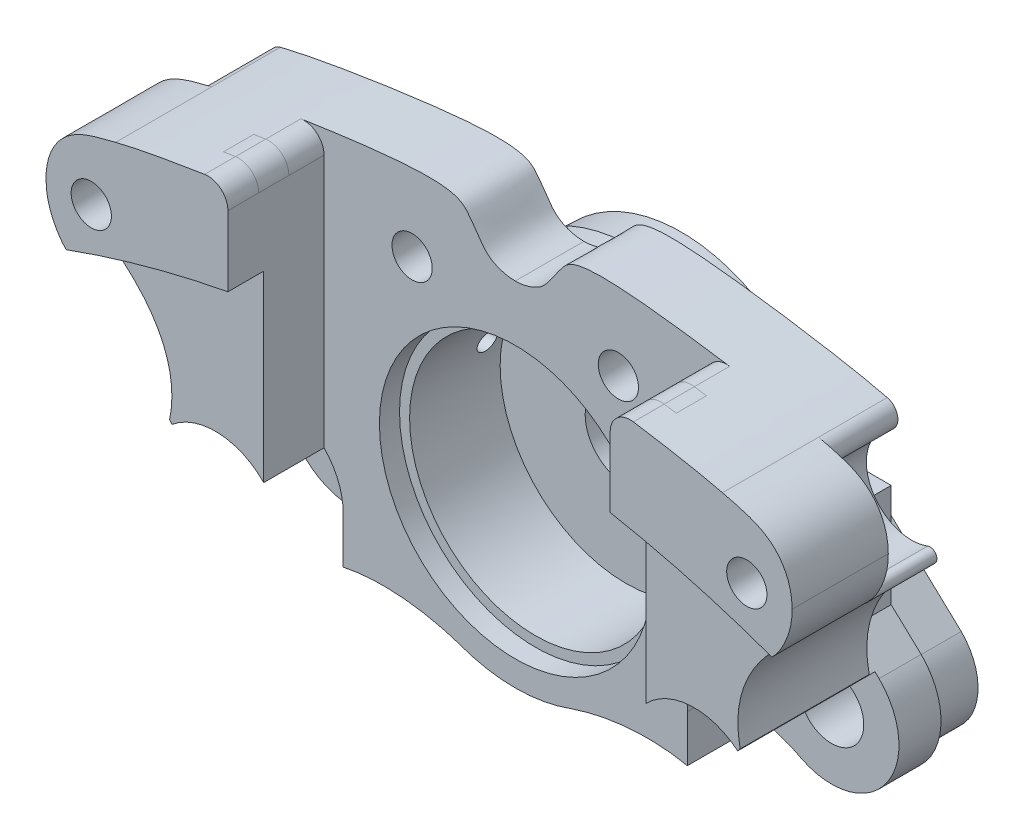
SolidWorks part; units mm, degrees
material "6061 Alloy"
ref_plane "Front Plane" through (0, 0, 0) normal (0, 0, 1) x (1, 0, 0)
ref_plane "Top Plane" through (0, 0, 0) normal (0, 1, 0) x (1, 0, 0)
ref_plane "Right Plane" through (0, 0, 0) normal (1, 0, 0) x (0, 0, -1)
sketch "Sketch1" plane through (0, 0, 0) normal (0, 0, 1) x (1, 0, 0)
  circle A0 centre (0, 0) radius 9.7028
  dimension "D1" = 19.4056
extrude "Boss-Extrude1" add sketch "Sketch1" along normal blind 4.8514
sketch "Sketch2" plane through (0, 0, 4.8514) normal (0, 0, 1) x (1, 0, 0)
  line L0 (0, 15.875) -> (0, -12.065) construction
  line L1 (-30.226, -12.065) -> (30.226, -12.065) construction
  line L2 (-13.4704, 13.4704) -> (-35.3447, -6.9463)
  line L3 (13.4704, 13.4704) -> (35.3447, -6.9463)
  line L4 (0, 0) -> (13.4704, 13.4704) construction
  line L5 (0, 0) -> (-13.4704, 13.4704) construction
  line L8 (15.9939, -16.129) -> (17.3992, -16.129) construction
  line L14 (-17.3992, -16.129) -> (-15.9939, -16.129) construction
  arc A1 (-6.8392, -17.78) -> (6.8392, -17.78) centre (0, 0) ccw
  arc A4 (26.7503, -18.415) -> (35.3447, -6.9463) centre (30.226, -12.065) ccw
  arc A5 (-35.3447, -6.9463) -> (-26.7503, -18.415) centre (-30.226, -12.065) ccw
  arc A7 (13.4704, 13.4704) -> (-13.4704, 13.4704) centre (0, 0) ccw
  spline S0 degree 3 poles (-26.7503, -18.415) (-20.9125, -15.2196) (-12.826, -15.7036) (-6.8392, -17.78) knots 0 0 0 0 1 1 1 1
  spline S1 degree 3 poles (26.7503, -18.415) (20.9125, -15.2196) (12.826, -15.7036) (6.8392, -17.78) knots 0 0 0 0 1 1 1 1
  dimension "D2" = 38.1
  dimension "D6" = 6.35
  dimension "D3" = 27.94
  dimension "D4" = 60.452
  dimension "D5" = 30.226
  dimension "D9" = 17.78
extrude "Boss-Extrude2" add sketch "Sketch2" along normal blind 1.778 and the other way blind 4.1656
sketch "Sketch3" plane through (0, 0, 6.6294) normal (0, 0, 1) x (1, 0, 0)
  line L0 (-14.3527, 14.3841) -> (-18.4698, 10.5414)
  line L1 (36.2267, -6.0322) -> (32.4398, -2.4977)
  line L2 (18.4698, 10.5414) -> (14.3527, 14.3841)
  line L6 (0, 19.05) -> (0, -19.05) construction
  line L7 (18.4698, 10.5414) -> (32.4398, 10.5414)
  line L8 (32.4398, 10.5414) -> (32.4398, -2.4977)
  line L9 (-32.4398, 10.5414) -> (-32.4398, -2.4977)
  line L10 (-18.4698, 10.5414) -> (-32.4398, 10.5414)
  line L11 (-32.4398, -2.4977) -> (-36.2267, -6.0322)
  arc A0 (-36.2267, -6.0322) -> (-26.4195, -19.6751) centre (-30.226, -12.065) ccw
  arc A1 (-7.0511, -19.0574) -> (7.0511, -19.0574) centre (0, 0) ccw
  arc A2 (26.4195, -19.6751) -> (36.2267, -6.0322) centre (30.226, -12.065) ccw
  arc A3 (14.3527, 14.3841) -> (-14.3527, 14.3841) centre (0, 0) ccw
  circle A12 centre (0, 0) radius 15.875 construction
  spline S6 degree 3 poles (-26.4195, -19.6751) (-25.7261, -19.2934) (-24.2904, -18.6475) (-21.15, -17.7332) (-17.755, -17.383) (-14.3154, -17.5158) (-11.771, -17.8352) (-9.7297, -18.2634) (-8.1656, -18.6925) (-7.4233, -18.9297) (-7.0511, -19.0574) knots 0 0 0 0 0.124858 0.249716 0.499432 0.62429 0.749148 0.874006 0.936435 0.998864 0.998864 0.998864 0.998864
  spline S7 degree 3 poles (7.0511, -19.0574) (7.4233, -18.9297) (8.1656, -18.6925) (9.7297, -18.2634) (11.771, -17.8352) (14.3154, -17.5158) (17.755, -17.383) (21.15, -17.7332) (24.2904, -18.6475) (25.7261, -19.2934) (26.4195, -19.6751) knots 0.001136 0.001136 0.001136 0.001136 0.063565 0.125994 0.250852 0.37571 0.500568 0.750284 0.875142 1 1 1 1
  dimension "D3" = 31.75
  dimension "D4" = 13.97
extrude "Boss-Extrude3" add sketch "Sketch3" along normal blind 6.35
sketch "Sketch5" plane through (0, 0, 12.9794) normal (0, 0, 1) x (1, 0, 0)
  line L0 (-41.3748, 17.9058) -> (0, 17.9058) construction
  line L1 (0, 0) -> (0, 17.9058) construction
  line L2 (0, 17.9058) -> (0, 24.1687) construction
  line L3 (1.2486, 24.1687) -> (-1.2486, 24.1687) construction
  line L4 (-35.6955, -5.5467) -> (-36.0146, -5.1665)
  line L5 (35.6955, -5.5467) -> (36.0146, -5.1665)
  line L7 (-30.226, -12.065) -> (30.226, -12.065) construction
  line L8 (-21.717, -12.065) -> (-21.717, -17.9655)
  line L9 (21.717, -12.065) -> (21.717, -17.9655)
  arc A0 (-43.3944, 12.5595) -> (-38.6973, 22.9547) centre (-41.3748, 17.9058) ccw
  arc A1 (-43.3944, 12.5595) -> (-44.0085, 10.9339) centre (-43.7015, 11.7467) ccw
  arc A2 (43.3944, 12.5595) -> (44.0085, 10.9339) centre (43.7015, 11.7467) cw
  arc A3 (-7.0511, -19.0574) -> (7.0511, -19.0574) centre (0, 0) ccw construction
  arc A4 (38.2982, 26.2485) -> (38.6973, 22.9547) centre (37.8646, 24.5249) cw
  arc A5 (-38.2982, 26.2485) -> (-38.6973, 22.9547) centre (-37.8646, 24.5249) ccw
  arc A6 (43.3944, 12.5595) -> (38.6973, 22.9547) centre (41.3748, 17.9058) cw
  arc A7 (-7.0511, -19.0574) -> (7.0511, -19.0574) centre (0, 0) ccw
  arc A8 (35.6955, -5.5467) -> (21.717, -12.065) centre (30.226, -12.065) ccw
  arc A9 (-21.717, -12.065) -> (-35.6955, -5.5467) centre (-30.226, -12.065) ccw
  arc A10 (-36.2267, -6.0322) -> (-26.4195, -19.6751) centre (-30.226, -12.065) ccw construction
  arc A11 (26.4195, -19.6751) -> (36.2267, -6.0322) centre (30.226, -12.065) ccw construction
  spline S0 degree 3 poles (-38.2982, 26.2485) (-33.1754, 27.5373) (-13.115, 30.6549) (-7.0965, 29.9705) (-4.5847, 26.9765) (-3.9197, 25.0203) (-1.0614, 24.1687) (0, 24.1687) knots 0.095992 0.095992 0.095992 0.095992 0.290427 0.440824 0.493566 0.817843 1 1 1 1
  spline S1 degree 3 poles (-44.0085, 10.9339) (-41.4119, 8.9019) (-37.0603, 4.9292) (-35.1847, -1.262) (-36.0146, -5.1665) knots 0.120959 0.120959 0.120959 0.120959 0.469292 0.87789 0.87789 0.87789 0.87789
  spline S2 degree 3 poles (44.0085, 10.9339) (41.4119, 8.9019) (37.0603, 4.9292) (35.1847, -1.262) (36.0146, -5.1665) knots 0.120959 0.120959 0.120959 0.120959 0.469292 0.87789 0.87789 0.87789 0.87789
  spline S3 degree 3 poles (38.2982, 26.2485) (33.1754, 27.5373) (13.115, 30.6549) (7.0965, 29.9705) (4.5847, 26.9765) (3.9197, 25.0203) (1.0614, 24.1687) (0, 24.1687) knots 0.095992 0.095992 0.095992 0.095992 0.290427 0.440824 0.493566 0.817843 1 1 1 1
  spline S5 degree 3 poles (-978.7255, -1777.5091) (-16.9448, -159.6111) (-62.0704, -29.6471) (-21.15, -17.7332) (-17.755, -17.383) (-14.3154, -17.5158) (-11.771, -17.8352) (-9.7297, -18.2634) (13.3146, -24.5869) (3.4509, -48.9429) (1868.6439, -712.6762) knots -6.008282 -6.008282 -6.008282 -6.008282 0.124858 0.249716 0.499432 0.62429 0.749148 0.874006 0.936435 4.428366 4.428366 4.428366 4.428366 only from (-26.4195, -19.6751) to (-7.0511, -19.0574) construction
  spline S6 degree 3 poles (7.0511, -19.0574) (7.4233, -18.9297) (8.1656, -18.6925) (9.7297, -18.2634) (11.771, -17.8352) (14.3154, -17.5158) (17.6851, -17.3857) (20.1633, -17.6317) (21.717, -17.9655) knots 0.001136 0.001136 0.001136 0.001136 0.063565 0.125994 0.250852 0.37571 0.500568 0.740144 0.740144 0.740144 0.740144
  spline S7 degree 3 poles (-21.717, -17.9655) (-20.1633, -17.6317) (-17.6851, -17.3857) (-14.3154, -17.5158) (-11.771, -17.8352) (-9.7297, -18.2634) (-8.1656, -18.6925) (-7.4233, -18.9297) (-7.0511, -19.0574) knots 0.259856 0.259856 0.259856 0.259856 0.499432 0.62429 0.749148 0.874006 0.936435 0.998864 0.998864 0.998864 0.998864
  dimension "D1" = 130
  dimension "D2" = 130
extrude "Boss-Extrude6" add sketch "Sketch5" along normal blind 8.6614
sketch "Sketch6" plane through (0, 0, 21.6408) normal (0, 0, 1) x (1, 0, 0)
  line L0 (0, 0) -> (0, 15.7134) construction
  line L2 (-36.0146, -5.1665) -> (-35.6955, -5.5467) construction
  line L3 (-36.0146, -5.1665) -> (-35.6955, -5.5467)
  line L4 (-36.0146, -5.1665) -> (-35.6955, -5.5467)
  line L5 (35.6955, -5.5467) -> (36.0146, -5.1665) construction
  line L6 (35.6955, -5.5467) -> (36.0146, -5.1665)
  line L11 (-21.717, -12.065) -> (-21.717, -17.9655)
  line L12 (-21.717, -12.065) -> (-21.717, -17.9655)
  line L13 (21.717, -17.9655) -> (21.717, -12.065)
  line L14 (21.717, -17.9655) -> (21.717, -12.065)
  line L15 (35.6955, -5.5467) -> (36.0146, -5.1665)
  arc A0 (-7.0511, -19.0574) -> (7.0511, -19.0574) centre (0, 0) ccw construction
  arc A2 (-7.0511, -19.0574) -> (7.0511, -19.0574) centre (0, 0) ccw
  arc A9 (-38.2982, 26.2485) -> (-38.6973, 22.9547) centre (-37.8646, 24.5249) ccw
  arc A10 (-43.3944, 12.5595) -> (-38.6973, 22.9547) centre (-41.3748, 17.9058) ccw
  arc A11 (-43.3944, 12.5595) -> (-44.0085, 10.9339) centre (-43.7015, 11.7467) ccw
  arc A12 (-21.717, -12.065) -> (-35.6955, -5.5467) centre (-30.226, -12.065) ccw
  arc A14 (-21.717, -12.065) -> (-35.6955, -5.5467) centre (-30.226, -12.065) ccw
  arc A15 (44.0085, 10.9339) -> (43.3944, 12.5595) centre (43.7015, 11.7467) ccw
  arc A16 (38.6973, 22.9547) -> (43.3944, 12.5595) centre (41.3748, 17.9058) ccw
  arc A17 (38.6973, 22.9547) -> (38.2982, 26.2485) centre (37.8646, 24.5249) ccw
  arc A19 (-7.0511, -19.0574) -> (7.0511, -19.0574) centre (0, 0) ccw
  arc A25 (35.6955, -5.5467) -> (21.717, -12.065) centre (30.226, -12.065) ccw
  arc A26 (35.6955, -5.5467) -> (21.717, -12.065) centre (30.226, -12.065) ccw
  spline S0 degree 3 poles (-38.2982, 26.2485) (-40.3087, 25.7427) (-44.7917, 24.769) (-47.0898, 20.7135) (-47.0898, 17.9058) knots 0 0 0 0 0.465439 1 1 1 1
  spline S1 degree 3 poles (-47.0898, 17.9058) (-47.0898, 16.2266) (-46.4199, 13.9412) (-45.0511, 11.7499) (-44.0085, 10.9339) knots 0 0 0 0 0.544279 1 1 1 1
  spline S2 degree 3 poles (47.0898, 17.9058) (47.0898, 16.2266) (46.4199, 13.9412) (45.0511, 11.7499) (44.0085, 10.9339) knots 0 0 0 0 0.544279 1 1 1 1
  spline S3 degree 3 poles (38.2982, 26.2485) (40.3087, 25.7427) (44.7917, 24.769) (47.0898, 20.7135) (47.0898, 17.9058) knots 0 0 0 0 0.465439 1 1 1 1
  spline S4 degree 3 poles (-657.2117, 1910.6164) (-193.2792, -28.4777) (64.9588, 100.6233) (-94.862, -144.8705) (-2021.4839, -219.0001) knots -4.624316 -4.624316 -4.624316 -4.624316 0.469292 5.21147 5.21147 5.21147 5.21147 only from (-44.0085, 10.9339) to (-36.0146, -5.1665) construction
  spline S6 degree 3 poles (-2183.245, 2077.1816) (166.4827, 62.4672) (0.5629, 11.8331) (-4.5847, 26.9765) (-7.0965, 29.9705) (-30.8647, 32.6733) (-341.1745, -36.5716) (2935.9323, 415.7326) knots -3.67352 -3.67352 -3.67352 -3.67352 0.278149 0.602426 0.655168 0.805566 2.172513 2.172513 2.172513 2.172513 only from (0, 24.1687) to (-38.2982, 26.2485)
  spline S7 degree 3 poles (-408.6307, 942.0868) (-142.5011, -5.0132) (25.7847, 65.0404) (-66.3745, -98.2734) (-1022.8759, -166.7155) knots -3.564937 -3.564937 -3.564937 -3.564937 0.469292 4.198398 4.198398 4.198398 4.198398 only from (-44.0085, 10.9339) to (-36.0146, -5.1665)
  spline S8 degree 3 poles (773.9984, -623.6344) (-88.6459, -105.5622) (-56.1182, -15.9019) (-14.3154, -17.5158) (-11.771, -17.8352) (-9.7297, -18.2634) (8.744, -23.3327) (6.1469, -39.711) (927.5284, -374.7025) knots -5.320743 -5.320743 -5.320743 -5.320743 0.499432 0.62429 0.749148 0.874006 0.936435 3.698622 3.698622 3.698622 3.698622 only from (-21.717, -17.9655) to (-7.0511, -19.0574)
  spline S10 degree 3 poles (1022.878, -166.7156) (66.3745, -98.2735) (-25.7847, 65.0403) (142.501, -5.0132) (408.6302, 942.085) knots -3.199551 -3.199551 -3.199551 -3.199551 0.529557 4.563784 4.563784 4.563784 4.563784 only from (36.0146, -5.1665) to (44.0085, 10.9339)
  spline S11 degree 3 poles (-2936.0853, 415.7537) (341.1832, -36.5735) (30.865, 32.6733) (7.0965, 29.9705) (4.5847, 26.9765) (-0.5628, 11.8332) (-166.4811, 62.4666) (2183.2062, 2077.1484) knots -1.076542 -1.076542 -1.076542 -1.076542 0.290427 0.440824 0.493566 0.817843 4.76949 4.76949 4.76949 4.76949 only from (38.2982, 26.2485) to (0, 24.1687)
  spline S12 degree 3 poles (0, 24.1687) (-1.0614, 24.1687) (-3.9197, 25.0203) (-4.5847, 26.9765) (-7.0965, 29.9705) (-13.115, 30.6549) (-33.1754, 27.5373) (-38.2982, 26.2485) knots 0.095992 0.095992 0.095992 0.095992 0.278149 0.602426 0.655168 0.805566 1 1 1 1
  spline S13 degree 3 poles (2021.4462, -218.9987) (94.861, -144.8689) (-64.9585, 100.6237) (193.281, -28.4786) (657.2209, 1910.6551) knots -4.212589 -4.212589 -4.212589 -4.212589 0.529557 5.6232 5.6232 5.6232 5.6232 only from (36.0146, -5.1665) to (44.0085, 10.9339) construction
  spline S14 degree 3 poles (-44.0085, 10.9339) (-41.4119, 8.9019) (-37.0603, 4.9292) (-35.1847, -1.262) (-36.0146, -5.1665) knots 0.120959 0.120959 0.120959 0.120959 0.469292 0.87789 0.87789 0.87789 0.87789
  spline S15 degree 3 poles (-1868.6977, -712.6953) (-3.4507, -48.9434) (-13.3148, -24.587) (9.7297, -18.2634) (11.771, -17.8352) (14.3154, -17.5158) (66.5225, -15.5003) (104.6343, -157.023) (-1642.0572, -1120.0359) knots -3.428399 -3.428399 -3.428399 -3.428399 0.063565 0.125994 0.250852 0.37571 0.500568 7.831491 7.831491 7.831491 7.831491 only from (7.0511, -19.0574) to (21.717, -17.9655) construction
  spline S16 degree 3 poles (1642.0265, -1120.019) (-104.6338, -157.0214) (-66.5222, -15.5003) (-14.3154, -17.5158) (-11.771, -17.8352) (-9.7297, -18.2634) (13.3145, -24.5869) (3.451, -48.9427) (1868.6163, -712.6663) knots -6.831448 -6.831448 -6.831448 -6.831448 0.499432 0.62429 0.749148 0.874006 0.936435 4.428348 4.428348 4.428348 4.428348 only from (-21.717, -17.9655) to (-7.0511, -19.0574) construction
  spline S17 degree 3 poles (38.2982, 26.2485) (33.1754, 27.5373) (13.115, 30.6549) (7.0965, 29.9705) (4.5847, 26.9765) (3.9197, 25.0203) (1.0614, 24.1687) (0, 24.1687) knots 0.095992 0.095992 0.095992 0.095992 0.290427 0.440824 0.493566 0.817843 1 1 1 1
  spline S18 degree 3 poles (36.0146, -5.1665) (35.1847, -1.262) (37.0603, 4.9292) (41.4119, 8.9019) (44.0085, 10.9339) knots 0.120959 0.120959 0.120959 0.120959 0.529557 0.87789 0.87789 0.87789 0.87789
  spline S19 degree 3 poles (7.0511, -19.0574) (7.4233, -18.9297) (8.1656, -18.6925) (9.7297, -18.2634) (11.771, -17.8352) (14.3154, -17.5158) (17.6851, -17.3857) (20.1633, -17.6317) (21.717, -17.9655) knots 0.001136 0.001136 0.001136 0.001136 0.063565 0.125994 0.250852 0.37571 0.500568 0.740144 0.740144 0.740144 0.740144
  spline S20 degree 3 poles (-21.717, -17.9655) (-20.1633, -17.6317) (-17.6851, -17.3857) (-14.3154, -17.5158) (-11.771, -17.8352) (-9.7297, -18.2634) (-8.1656, -18.6925) (-7.4233, -18.9297) (-7.0511, -19.0574) knots 0.259856 0.259856 0.259856 0.259856 0.499432 0.62429 0.749148 0.874006 0.936435 0.998864 0.998864 0.998864 0.998864
  spline S26 degree 3 poles (-927.5625, -374.7149) (-6.1469, -39.7114) (-8.7442, -23.3328) (9.7297, -18.2634) (11.771, -17.8352) (14.3154, -17.5158) (56.1182, -15.9019) (88.6459, -105.5622) (-773.9984, -623.6344) knots -2.698656 -2.698656 -2.698656 -2.698656 0.063565 0.125994 0.250852 0.37571 0.500568 6.320743 6.320743 6.320743 6.320743 only from (7.0511, -19.0574) to (21.717, -17.9655)
  dimension "D1" = 0
extrude "Boss-Extrude8" add sketch "Sketch6" along normal blind 7.62
ref_plane "Plane5" through (0, 0, 29.2608) normal (0, 0, 1) x (1, 0, 0)
sketch "Sketch8" plane through (0, 0, 0) normal (0, 0, 1) x (1, 0, 0)
  line L0 (0, 0.0477) -> (0, -110.9255) construction
  line L1 (30.226, -12.065) -> (0, -110.9255) construction
  circle A0 centre (0, -110.9255) radius 103.378
  circle A1 centre (0, -110.9255) radius 142.4868
  circle A2 centre (0, 0.0477) radius 15.875
  arc A3 (44.0085, 10.9339) -> (44.4588, 11.3208) centre (40.0294, 16.0204) ccw
  arc A4 (44.0085, 10.9339) -> (44.4588, 11.3208) centre (40.0294, 16.0204) ccw
  arc A24 (44.0085, 10.9339) -> (44.4588, 11.3208) centre (43.7015, 11.7467) ccw
  arc A25 (44.0085, 10.9339) -> (44.4588, 11.3208) centre (43.7015, 11.7467) ccw
  spline S0 degree 3 poles (-38.2982, 26.2485) (-40.3087, 25.7427) (-44.7917, 24.769) (-47.0898, 20.7135) (-47.0898, 17.9058) knots 0 0 0 0 0.465439 1 1 1 1 construction
  dimension "D3" = 31.75
  dimension "D2" = 103.378
  dimension "D1" = 0
sketch "Sketch9" plane through (0, 0, 29.2608) normal (0, 0, 1) x (1, 0, 0)
  line L1 (-36.0146, -5.1665) -> (-35.6955, -5.5467)
  line L4 (-36.0146, -5.1665) -> (-35.6955, -5.5467)
  line L6 (-21.717, -12.065) -> (-21.717, -17.9655)
  line L7 (-21.717, -12.065) -> (-21.717, -17.9655)
  line L8 (21.717, -17.9655) -> (21.717, -12.065)
  line L9 (21.717, -17.9655) -> (21.717, -12.065)
  line L10 (35.6955, -5.5467) -> (36.0146, -5.1665)
  line L11 (35.6955, -5.5467) -> (36.0146, -5.1665)
  arc A0 (44.5354, 11.3943) -> (-44.5354, 11.3943) centre (0, -110.9255) ccw
  arc A4 (-21.717, -12.065) -> (-35.6955, -5.5467) centre (-30.226, -12.065) ccw
  arc A5 (-21.717, -12.065) -> (-35.6955, -5.5467) centre (-30.226, -12.065) ccw
  arc A6 (-7.0511, -19.0574) -> (7.0511, -19.0574) centre (0, 0) ccw
  arc A7 (-7.0511, -19.0574) -> (7.0511, -19.0574) centre (0, 0) ccw
  arc A8 (35.6955, -5.5467) -> (21.717, -12.065) centre (30.226, -12.065) ccw
  arc A9 (35.6955, -5.5467) -> (21.717, -12.065) centre (30.226, -12.065) ccw
  spline S8 degree 3 poles (-2936.0853, 415.7537) (341.1832, -36.5735) (30.865, 32.6733) (7.0965, 29.9705) (4.5847, 26.9765) (-0.5628, 11.8332) (-166.4811, 62.4666) (2183.2062, 2077.1484) knots -1.076542 -1.076542 -1.076542 -1.076542 0.290427 0.440824 0.493566 0.817843 4.76949 4.76949 4.76949 4.76949 only from (38.2982, 26.2485) to (0, 24.1687)
  spline S9 degree 3 poles (-2183.245, 2077.1816) (166.4827, 62.4672) (0.5629, 11.8331) (-4.5847, 26.9765) (-7.0965, 29.9705) (-30.8647, 32.6733) (-341.1745, -36.5716) (2935.9323, 415.7326) knots -3.67352 -3.67352 -3.67352 -3.67352 0.278149 0.602426 0.655168 0.805566 2.172513 2.172513 2.172513 2.172513 only from (0, 24.1687) to (-38.2982, 26.2485)
  spline S10 degree 3 poles (-1804.5999, 2450.3008) (126.3576, -108.3456) (-188.2093, 218.2385) (59.8858, -248.7813) (2928.1686, 292.6669) knots -6.919781 -6.919781 -6.919781 -6.919781 0.465439 9.127563 9.127563 9.127563 9.127563 only from (-38.2982, 26.2485) to (-47.0898, 17.9058)
  spline S11 degree 3 poles (1164.5757, 2762.169) (4.662, 68.9031) (-113.9279, 6.355) (35.9004, -20.0154) (2601.0359, 1424.5529) knots -9.618135 -9.618135 -9.618135 -9.618135 0.544279 9.981443 9.981443 9.981443 9.981443 only from (-47.0898, 17.9058) to (-44.0085, 10.9339)
  spline S12 degree 3 poles (-408.6307, 942.0868) (-142.5011, -5.0132) (25.7847, 65.0404) (-66.3745, -98.2734) (-1022.8759, -166.7155) knots -3.564937 -3.564937 -3.564937 -3.564937 0.469292 4.198398 4.198398 4.198398 4.198398 only from (-44.0085, 10.9339) to (-36.0146, -5.1665)
  spline S14 degree 3 poles (-2601.0264, 1424.5476) (-35.9002, -20.0154) (113.9276, 6.355) (-4.6615, 68.9028) (-1164.5625, 2762.1382) knots -8.981431 -8.981431 -8.981431 -8.981431 0.455721 10.618097 10.618097 10.618097 10.618097 only from (44.0085, 10.9339) to (47.0898, 17.9058)
  spline S15 degree 3 poles (-2928.182, 292.6694) (-59.8863, -248.7821) (188.2093, 218.2384) (-126.357, -108.345) (1804.5887, 2450.2859) knots -8.127576 -8.127576 -8.127576 -8.127576 0.534561 7.919767 7.919767 7.919767 7.919767 only from (47.0898, 17.9058) to (38.2982, 26.2485)
  spline S16 degree 3 poles (38.2982, 26.2485) (33.1754, 27.5373) (13.115, 30.6549) (7.0965, 29.9705) (4.5847, 26.9765) (3.9197, 25.0203) (1.0614, 24.1687) (0, 24.1687) knots 0.095992 0.095992 0.095992 0.095992 0.290427 0.440824 0.493566 0.817843 1 1 1 1
  spline S17 degree 3 poles (0, 24.1687) (-1.0614, 24.1687) (-3.9197, 25.0203) (-4.5847, 26.9765) (-7.0965, 29.9705) (-13.115, 30.6549) (-33.1754, 27.5373) (-38.2982, 26.2485) knots 0.095992 0.095992 0.095992 0.095992 0.278149 0.602426 0.655168 0.805566 1 1 1 1
  spline S18 degree 3 poles (-38.2982, 26.2485) (-40.3087, 25.7427) (-44.7917, 24.769) (-47.0898, 20.7135) (-47.0898, 17.9058) knots 0 0 0 0 0.465439 1 1 1 1
  spline S19 degree 3 poles (-47.0898, 17.9058) (-47.0898, 16.2266) (-46.4752, 14.1298) (-45.2723, 12.1122) (-44.5354, 11.3943) knots 0 0 0 0 0.544279 0.917463 0.917463 0.917463 0.917463
  spline S21 degree 3 poles (2522.3306, -1594.3353) (-115.2586, -200.4108) (-73.8617, -15.2169) (-14.3154, -17.5158) (-11.771, -17.8352) (-9.7297, -18.2634) (16.5073, -25.463) (-0.039, -56.304) (2811.2395, -1046.1766) knots -7.897157 -7.897157 -7.897157 -7.897157 0.499432 0.62429 0.749148 0.874006 0.936435 4.9381 4.9381 4.9381 4.9381 only from (-21.717, -17.9655) to (-7.0511, -19.0574)
  spline S22 degree 3 poles (44.5354, 11.3943) (45.2723, 12.1122) (46.4752, 14.1298) (47.0898, 16.2266) (47.0898, 17.9058) knots 0.082537 0.082537 0.082537 0.082537 0.455721 1 1 1 1
  spline S23 degree 3 poles (47.0898, 17.9058) (47.0898, 20.7135) (44.7917, 24.769) (40.3087, 25.7427) (38.2982, 26.2485) knots 0 0 0 0 0.534561 1 1 1 1
  spline S24 degree 3 poles (-21.717, -17.9655) (-20.1633, -17.6317) (-17.6851, -17.3857) (-14.3154, -17.5158) (-11.771, -17.8352) (-9.7297, -18.2634) (-8.1656, -18.6925) (-7.4233, -18.9297) (-7.0511, -19.0574) knots 0.259856 0.259856 0.259856 0.259856 0.499432 0.62429 0.749148 0.874006 0.936435 0.998864 0.998864 0.998864 0.998864
  spline S25 degree 3 poles (-2811.3078, -1046.2007) (0.0392, -56.3045) (-16.5075, -25.4631) (9.7297, -18.2634) (11.771, -17.8352) (14.3154, -17.5158) (73.8618, -15.2169) (115.2588, -200.4118) (-2522.3522, -1594.3467) knots -3.938132 -3.938132 -3.938132 -3.938132 0.063565 0.125994 0.250852 0.37571 0.500568 8.897179 8.897179 8.897179 8.897179 only from (7.0511, -19.0574) to (21.717, -17.9655)
  spline S26 degree 3 poles (7.0511, -19.0574) (7.4233, -18.9297) (8.1656, -18.6925) (9.7297, -18.2634) (11.771, -17.8352) (14.3154, -17.5158) (17.6851, -17.3857) (20.1633, -17.6317) (21.717, -17.9655) knots 0.001136 0.001136 0.001136 0.001136 0.063565 0.125994 0.250852 0.37571 0.500568 0.740144 0.740144 0.740144 0.740144
  spline S28 degree 3 poles (1022.878, -166.7156) (66.3745, -98.2735) (-25.7847, 65.0403) (142.501, -5.0132) (408.6302, 942.085) knots -3.199551 -3.199551 -3.199551 -3.199551 0.529557 4.563784 4.563784 4.563784 4.563784 only from (36.0146, -5.1665) to (44.0085, 10.9339)
  dimension "D1" = 260.35
  dimension "D2" = 0
extrude "Boss-Extrude9" add sketch "Sketch9" along normal blind 4.5212 contours S22 S23 S16 S17 S18 S19 A0 region at (0, 21.9757, 29.2608)
sketch "Sketch10" plane through (0, 0, 0) normal (0, 1, 0) x (1, 0, 0)
  line L1 (-24.13, -45.9232) -> (24.13, -45.9232)
  line L2 (-24.13, -45.9232) -> (-24.13, -21.6408)
  line L3 (-24.13, -21.6408) -> (24.13, -21.6408)
  line L4 (24.13, -45.9232) -> (24.13, -21.6408)
  line L5 (-24.13, -45.9232) -> (24.13, -21.6408) construction
  line L6 (-24.13, -21.6408) -> (24.13, -45.9232) construction
  point P0 (0, -33.782)
  dimension "D2" = 48.26
extrude "Cut-Extrude1" cut sketch "Sketch10" against normal mid plane 127
sketch "Sketch11" plane through (0, 0, 0.6858) normal (0, 0, -1) x (-1, 0, 0)
  line L0 (0, 0) -> (0, 20.32) construction
  line L1 (-13.0136, 20.32) -> (13.0136, 20.32) construction
  circle A0 centre (-13.0136, 20.32) radius 5.08
  circle A1 centre (13.0136, 20.32) radius 5.08
  arc A3 (13.4704, 13.4704) -> (-13.4704, 13.4704) centre (0, 0) ccw construction
  dimension "D1" = 10.16
extrude "Cut-Extrude2" cut sketch "Sketch11" against normal up to surface (12.2936 mm away) up to face at (1.4431, 10.3095, 12.9794)
sketch "Sketch12" plane through (0, 0, 21.6408) normal (0, 0, -1) x (-1, 0, 0)
  line L0 (0, 0) -> (0, 32.3308) construction
  circle A2 centre (41.3748, 17.9058) radius 2.54
  circle A3 centre (-41.3748, 17.9058) radius 2.54
  dimension "D1" = 5.08
extrude "Cut-Extrude3" cut sketch "Sketch12" against normal through all
sketch "Sketch13" plane through (0, 0, 12.9794) normal (0, 0, -1) x (-1, 0, 0)
  line L0 (0, 0) -> (0, 20.32) construction
  line L1 (-13.0175, 20.32) -> (13.0175, 20.32) construction
  circle A2 centre (13.0175, 20.32) radius 2.54
  circle A3 centre (-13.0175, 20.32) radius 2.54
  dimension "D1" = 5.08
  dimension "D2" = 20.32
  dimension "D3" = 26.035
extrude "Cut-Extrude4" cut sketch "Sketch13" against normal through all
sketch "Sketch14" plane through (0, 0, 0) normal (0, 1, 0) x (1, 0, 0)
  line L0 (0, -21.6408) -> (0, -27.9908) construction
  line L1 (-28.575, -29.8958) -> (28.575, -29.8958)
  line L2 (-28.575, -29.8958) -> (-28.575, -26.0858)
  line L3 (-28.575, -26.0858) -> (28.575, -26.0858)
  line L4 (28.575, -29.8958) -> (28.575, -26.0858)
  line L5 (-28.575, -29.8958) -> (28.575, -26.0858) construction
  line L6 (-28.575, -26.0858) -> (28.575, -29.8958) construction
  point P0 (0, -27.9908)
  dimension "D1" = 57.15
  dimension "D2" = 3.81
  dimension "D3" = 6.35
split line "Split Line1"
sketch "Sketch15" plane through (0, 0, 0) normal (0, 0, -1) x (-1, 0, 0)
  circle A0 centre (0, 0) radius 15.875
  dimension "D1" = 31.75
extrude "Cut-Extrude5" cut sketch "Sketch15" along normal blind 13.97 from surface starting at face at (10.4775, 20.32, 21.6408)
sketch "Sketch16" plane through (-32.4398, 0, 0) normal (-1, 0, 0) x (0, 0, 1)
  line L0 (12.9794, 10.5414) -> (6.6294, -2.4977) construction
  line L1 (6.6294, 10.5414) -> (12.9794, -2.4977) construction
  line L4 (12.9794, 10.5414) -> (6.6294, 10.5414)
  line L5 (6.6294, 10.5414) -> (6.6294, -2.4977)
  line L6 (6.6294, -2.4977) -> (12.9794, -2.4977)
  line L7 (6.6294, 10.5414) -> (6.6294, -2.4977)
  line L8 (12.9794, 10.5414) -> (6.6294, 10.5414) construction
  line L9 (12.9794, -2.4977) -> (12.9794, 10.5414)
  line L10 (6.6294, -2.4977) -> (12.9794, -2.4977) construction
  line L11 (12.9794, -2.4977) -> (12.9794, 10.5414)
  circle A0 centre (9.8044, 4.0218) radius 1.27
  dimension "D2" = 2.54
  dimension "D1" = 0
extrude "Cut-Extrude6" cut sketch "Sketch16" against normal through all contours A0 region at (-32.4398, 4.0218, 9.8044)
fillet "Fillet5" radius 2.54 6 edges at (24.13, 28.8083, 31.8389) (24.13, 28.8083, 27.9908) (24.13, 28.8083, 23.8633) (-24.13, 28.8083, 31.8389) (-24.13, 28.8083, 23.8633) (-24.13, 28.8083, 27.9908)
sketch "Sketch17" plane through (0, 0, 21.6408) normal (0, 0, 1) x (1, 0, 0)
  circle A0 centre (0, 0) radius 17.145
  dimension "D1" = 34.29
extrude "Cut-Extrude7" cut sketch "Sketch17" against normal blind 2.54
sketch "Sketch18" plane through (0, 0, 21.6408) normal (0, 0, 1) x (1, 0, 0)
  circle A0 centre (-30.226, -12.065) radius 4.064
  circle A1 centre (30.226, -12.065) radius 4.064
  dimension "D1" = 60.452
extrude "Cut-Extrude8" cut sketch "Sketch18" against normal through all
sketch "Sketch19" plane through (0, 0, 12.9794) normal (0, 0, 1) x (1, 0, 0)
  line L0 (35.7004, -5.5409) -> (35.6955, -5.5467) construction
  line L1 (21.717, -12.065) -> (21.717, -17.9655) construction
  line L2 (36.2267, -6.0322) -> (35.7004, -5.5409) construction
  line L3 (-21.717, -17.9655) -> (-21.717, -12.065) construction
  line L4 (-35.6955, -5.5467) -> (-35.7004, -5.5409) construction
  line L5 (-35.7004, -5.5409) -> (-36.2267, -6.0322) construction
  line L6 (35.7004, -5.5409) -> (35.6955, -5.5467)
  line L7 (21.717, -12.065) -> (21.717, -17.9655)
  line L8 (36.2267, -6.0322) -> (35.7004, -5.5409)
  line L9 (-21.717, -17.9655) -> (-21.717, -12.065)
  line L10 (-35.6955, -5.5467) -> (-35.7004, -5.5409)
  line L11 (-35.7004, -5.5409) -> (-36.2267, -6.0322)
  arc A0 (35.6955, -5.5467) -> (21.717, -12.065) centre (30.226, -12.065) ccw construction
  arc A1 (26.4195, -19.6751) -> (36.2267, -6.0322) centre (30.226, -12.065) ccw construction
  arc A2 (-21.717, -12.065) -> (-35.6955, -5.5467) centre (-30.226, -12.065) ccw construction
  arc A3 (-36.2267, -6.0322) -> (-26.4195, -19.6751) centre (-30.226, -12.065) ccw construction
  arc A4 (35.6955, -5.5467) -> (21.717, -12.065) centre (30.226, -12.065) ccw
  arc A5 (26.4195, -19.6751) -> (36.2267, -6.0322) centre (30.226, -12.065) ccw
  arc A6 (-21.717, -12.065) -> (-35.6955, -5.5467) centre (-30.226, -12.065) ccw
  arc A7 (-36.2267, -6.0322) -> (-26.4195, -19.6751) centre (-30.226, -12.065) ccw
  spline S0 degree 3 poles (1985.6086, 347.6562) (-171.9483, -192.2646) (-28.2052, -3.3634) (62.07, -29.647) (16.9457, -159.6086) (978.6976, -1777.4621) knots -7.348564 -7.348564 -7.348564 -7.348564 0.750284 0.875142 7.008223 7.008223 7.008223 7.008223 only from (21.717, -17.9655) to (26.4195, -19.6751) construction
  spline S1 degree 3 poles (-978.7111, -1777.4849) (-16.9453, -159.6098) (-62.0702, -29.6471) (28.2048, -3.3636) (171.9458, -192.2613) (-1985.5513, 347.6419) knots -6.008252 -6.008252 -6.008252 -6.008252 0.124858 0.249716 8.348493 8.348493 8.348493 8.348493 only from (-26.4195, -19.6751) to (-21.717, -17.9655) construction
  spline S2 degree 3 poles (21.717, -17.9655) (21.7828, -17.9796) (22.6564, -18.1718) (24.2904, -18.6475) (25.7261, -19.2934) (26.4195, -19.6751) knots 0.740144 0.740144 0.740144 0.740144 0.750284 0.875142 1 1 1 1
  spline S3 degree 3 poles (-26.4195, -19.6751) (-25.7261, -19.2934) (-24.2904, -18.6475) (-22.6564, -18.1718) (-21.7828, -17.9796) (-21.717, -17.9655) knots 0 0 0 0 0.124858 0.249716 0.259856 0.259856 0.259856 0.259856
extrude "Cut-Extrude9" cut sketch "Sketch19" against normal blind 1.0414
sketch "Sketch20" plane through (0, 0, 0) normal (0, 0, -1) x (-1, 0, 0)
  circle A0 centre (0, 0) radius 5.1435
  dimension "D1" = 10.287
extrude "Cut-Extrude10" cut sketch "Sketch20" against normal through all contours A0
cosmetic thread "Cosmetic Thread1" parameters "D2"=12.7
move or copy body "Body-Move/Copy1" [suppressed] bodies to move or copy 129
